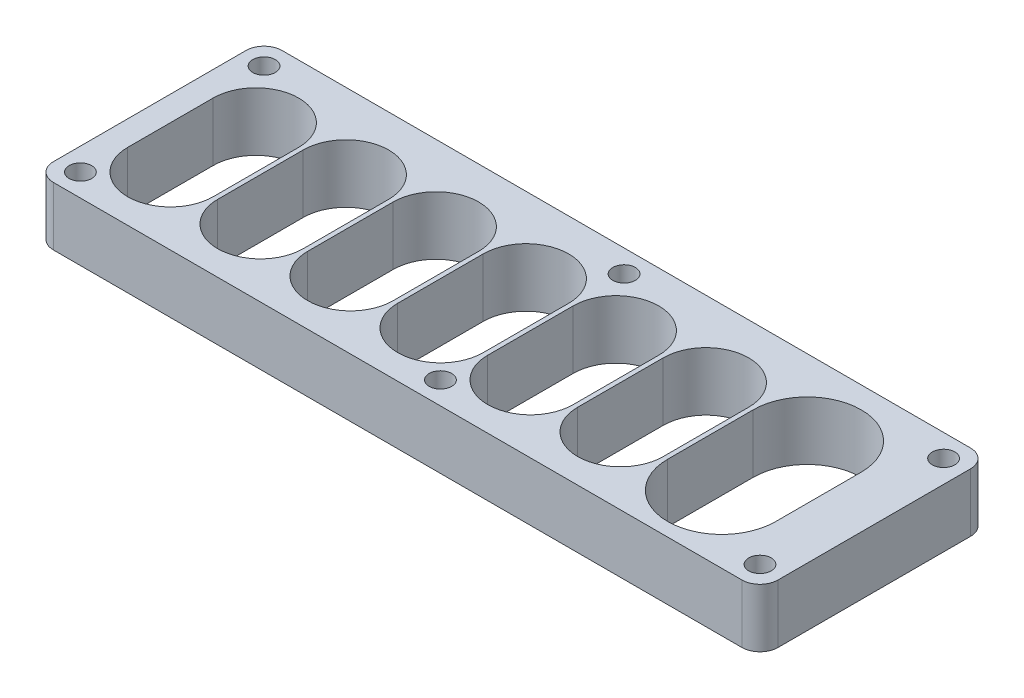
SolidWorks part; units mm, degrees
material "PE High Density"
ref_plane "Front Plane" through (0, 0, 0) normal (0, 0, 1) x (1, 0, 0)
ref_plane "Top Plane" through (0, 0, 0) normal (0, 1, 0) x (1, 0, 0)
ref_plane "Right Plane" through (0, 0, 0) normal (1, 0, 0) x (0, 0, -1)
sketch "Sketch1" plane through (0, 0, 0) normal (0, 1, 0) x (1, 0, 0)
  line L1 (-161, 0) -> (0, 0)
  line L2 (-161, 0) -> (-161, -50.8)
  line L3 (-161, -50.8) -> (0, -50.8)
  line L4 (0, 0) -> (0, -50.8)
  dimension "D1" = 161
  dimension "D2" = 50.8
extrude "Boss-Extrude1" add sketch "Sketch1" along normal blind 13
sketch "Sketch2" plane through (0, 13, 0) normal (0, 1, 0) x (1, 0, 0)
  line L0 (-146, -16.8) -> (-146, -35.8) construction
  line L1 (-136.5, -16.8) -> (-136.5, -35.8)
  line L2 (-155.5, -16.8) -> (-155.5, -35.8)
  line L3 (-161, 0) -> (-161, -50.8) construction
  line L4 (-161, -50.8) -> (0, -50.8) construction
  line L5 (-126, -16.8) -> (-126, -35.8) construction
  line L6 (-116.5, -16.8) -> (-116.5, -35.8)
  line L7 (-135.5, -16.8) -> (-135.5, -35.8)
  line L8 (-106, -16.8) -> (-106, -35.8) construction
  line L9 (-96.5, -16.8) -> (-96.5, -35.8)
  line L10 (-115.5, -16.8) -> (-115.5, -35.8)
  line L11 (-86, -16.8) -> (-86, -35.8) construction
  line L12 (-76.5, -16.8) -> (-76.5, -35.8)
  line L13 (-95.5, -16.8) -> (-95.5, -35.8)
  line L14 (-66, -16.8) -> (-66, -35.8) construction
  line L15 (-56.5, -16.8) -> (-56.5, -35.8)
  line L16 (-75.5, -16.8) -> (-75.5, -35.8)
  line L17 (-46, -16.8) -> (-46, -35.8) construction
  line L18 (-36.5, -16.8) -> (-36.5, -35.8)
  line L19 (-55.5, -16.8) -> (-55.5, -35.8)
  line L20 (-23.5, -16.8) -> (-23.5, -35.8) construction
  line L21 (-11.5, -16.8) -> (-11.5, -35.8)
  line L22 (-35.5, -16.8) -> (-35.5, -35.8)
  arc A0 (-136.5, -16.8) -> (-155.5, -16.8) centre (-146, -16.8) ccw
  arc A1 (-155.5, -35.8) -> (-136.5, -35.8) centre (-146, -35.8) ccw
  arc A2 (-116.5, -16.8) -> (-135.5, -16.8) centre (-126, -16.8) ccw
  arc A3 (-135.5, -35.8) -> (-116.5, -35.8) centre (-126, -35.8) ccw
  arc A4 (-96.5, -16.8) -> (-115.5, -16.8) centre (-106, -16.8) ccw
  arc A5 (-115.5, -35.8) -> (-96.5, -35.8) centre (-106, -35.8) ccw
  arc A6 (-76.5, -16.8) -> (-95.5, -16.8) centre (-86, -16.8) ccw
  arc A7 (-95.5, -35.8) -> (-76.5, -35.8) centre (-86, -35.8) ccw
  arc A8 (-56.5, -16.8) -> (-75.5, -16.8) centre (-66, -16.8) ccw
  arc A9 (-75.5, -35.8) -> (-56.5, -35.8) centre (-66, -35.8) ccw
  arc A10 (-36.5, -16.8) -> (-55.5, -16.8) centre (-46, -16.8) ccw
  arc A11 (-55.5, -35.8) -> (-36.5, -35.8) centre (-46, -35.8) ccw
  arc A12 (-11.5, -16.8) -> (-35.5, -16.8) centre (-23.5, -16.8) ccw
  arc A13 (-35.5, -35.8) -> (-11.5, -35.8) centre (-23.5, -35.8) ccw
  point P2 (-146, -26.3)
  point P13 (-126, -26.3)
  point P20 (-106, -26.3)
  point P27 (-86, -26.3)
  point P34 (-66, -26.3)
  point P41 (-46, -26.3)
  point P48 (-23.5, -26.3)
  dimension "D3" = 19
  dimension "D9" = 19
  dimension "D27" = 19
  dimension "D1" = 5.5
  dimension "D2" = 24.5
  dimension "D4" = 15
  dimension "D5" = 35
  dimension "D6" = 15
  dimension "D7" = 19
  dimension "D8" = 19
  dimension "D10" = 15
  dimension "D11" = 19
  dimension "D12" = 55
  dimension "D13" = 19
  dimension "D14" = 19
  dimension "D15" = 15
  dimension "D16" = 75
  dimension "D17" = 15
  dimension "D18" = 19
  dimension "D19" = 19
  dimension "D20" = 95
  dimension "D21" = 15
  dimension "D22" = 19
  dimension "D23" = 19
  dimension "D24" = 115
  dimension "D25" = 149.5
  dimension "D26" = 125.5
  dimension "D28" = 15
extrude "Cut-Extrude1" cut sketch "Sketch2" against normal through all
fillet "Fillet1" radius 4 4 edges at (-161, 6.5, 0) (-161, 6.5, 50.8) (0, 6.5, 0) (0, 6.5, 50.8)
hole_wizard "Ø5.0mm Dowel Hole1" positions "Sketch4" profile "Sketch3" hole size "Ø5.0" standard "ANSI Metric" end condition through all
sketch "Sketch4" plane through (0, 13, 0) normal (0, 1, 0) x (1, 0, 0)
  line L0 (-157, -50.8) -> (-4, -50.8) construction
  line L1 (-161, -4) -> (-161, -46.8) construction
  line L2 (-4, 0) -> (-157, 0) construction
  point P0 (-156, -45.8)
  point P2 (-76, -45.8)
  point P4 (-5, -45.8)
  point P6 (-5, -5)
  point P8 (-76, -5)
  point P10 (-156, -5)
  dimension "D1" = 5
  dimension "D2" = 5
  dimension "D3" = 5
  dimension "D4" = 80
  dimension "D5" = 71
sketch "Sketch3" plane through (-156, 13, 45.8) normal (1, 0, 0) x (0, 0, 1)
  line L0 (0, 0) -> (0, 13)
  line L1 (0, 13) -> (2.5, 13)
  line L2 (2.5, 13) -> (2.5, 0)
  line L5 (2.5, 0) -> (0, 0)
  line L11 (0, -6.35) -> (0, 107.95) construction
  dimension "Thru Hole Dia." = 5
  dimension "Thru Hole Depth" = 13
hole_wizard "Ø9.0 (9) Diameter Hole1" positions "Sketch8" profile "Sketch7" hole size "Ø9.0" standard "ANSI Metric"
sketch "Sketch8" plane through (0, 0, 0) normal (0, -1, 0) x (-1, 0, 0)
  point P0 (156, -45.8)
  point P3 (76, -45.8)
  point P6 (5, -45.8)
  point P9 (5, -5)
  point P12 (76, -5)
  point P15 (156, -5)
sketch "Sketch7" plane through (-156, 0, 45.8) normal (1, 0, 0) x (0, 0, -1)
  line L0 (0, 0) -> (0, 7.7039)
  line L1 (0, 7.7039) -> (4.5, 5)
  line L2 (4.5, 5) -> (4.5, 0)
  line L5 (4.5, 0) -> (0, 0)
  line L10 (0, 7.7039) -> (-4.5, 5) construction
  line L11 (0, -6.35) -> (0, 107.95) construction
  dimension "Hole Dia." = 9
  dimension "Hole Depth" = 5
  dimension "Drill Angle" = 118
